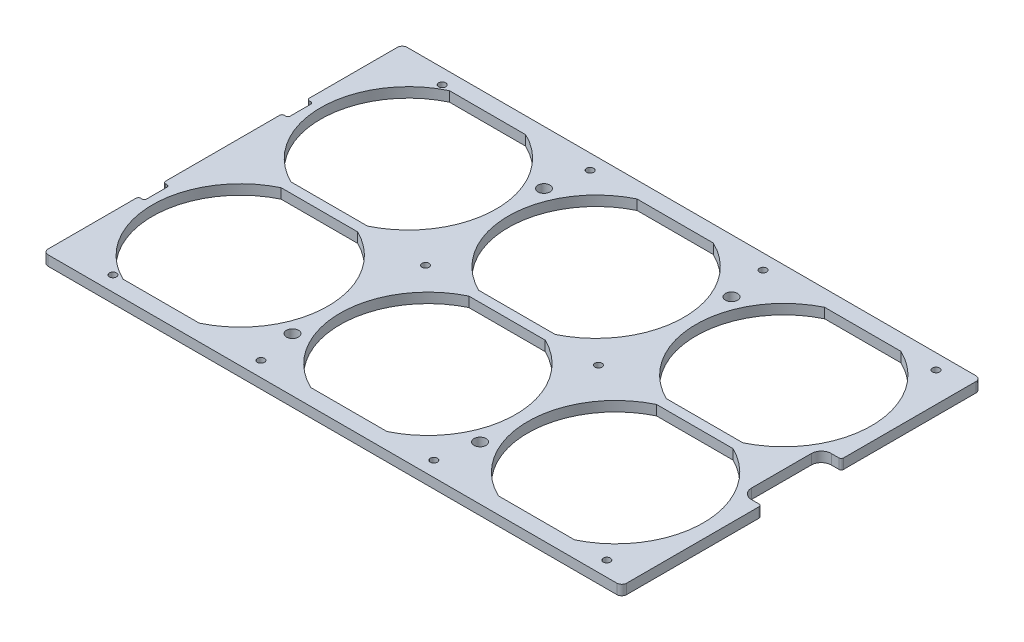
SolidWorks part; units mm, degrees
material "NEOPRENE"
ref_plane "Front" through (0, 0, 0) normal (0, 0, 1) x (1, 0, 0)
ref_plane "Top" through (0, 0, 0) normal (0, 1, 0) x (1, 0, 0)
ref_plane "Right" through (0, 0, 0) normal (1, 0, 0) x (0, 0, -1)
sketch "Sketch1" plane through (0, 0, 0) normal (0, 1, 0) x (1, 0, 0)
  line L0 (-24.3078, -3.1623) -> (24.3078, -3.1623)
  line L1 (-180.975, 114.3) -> (180.975, 114.3)
  line L2 (-184.15, 111.125) -> (-184.15, -111.125)
  line L3 (-180.975, -114.3) -> (180.975, -114.3)
  line L4 (184.15, 111.125) -> (184.15, -111.125)
  line L5 (-184.15, 114.3) -> (184.15, -114.3) construction
  line L6 (-184.15, -114.3) -> (184.15, 114.3) construction
  line L7 (95.1365, -3.1623) -> (143.7521, -3.1623)
  line L8 (95.1365, -3.1623) -> (95.1365, -103.8733) construction
  line L9 (95.1365, -103.8733) -> (143.7521, -103.8733)
  line L10 (143.7521, -3.1623) -> (143.7521, -103.8733) construction
  line L11 (95.1365, -3.1623) -> (143.7521, -103.8733) construction
  line L12 (95.1365, -103.8733) -> (143.7521, -3.1623) construction
  line L13 (-24.3078, -103.8733) -> (24.3078, -103.8733)
  line L14 (-143.7521, -3.1623) -> (-95.1365, -3.1623)
  line L15 (-143.7521, -103.8733) -> (-95.1365, -103.8733)
  line L16 (-24.3078, 103.8733) -> (24.3078, 103.8733)
  line L17 (-24.3078, 3.1623) -> (24.3078, 3.1623)
  line L18 (-143.7521, 103.8733) -> (-95.1365, 103.8733)
  line L19 (-143.7521, 3.1623) -> (-95.1365, 3.1623)
  line L20 (95.1365, 103.8733) -> (143.7521, 103.8733)
  line L21 (95.1365, 3.1623) -> (143.7521, 3.1623)
  line L22 (-95.1365, -103.8733) -> (-24.3078, -103.8733) construction
  line L23 (24.3078, -103.8733) -> (95.1365, -103.8733) construction
  line L24 (119.5086, 53.5178) -> (119.5086, -53.5178) construction
  line L25 (24.3078, 3.1623) -> (24.3078, -3.1623) construction
  line L26 (-175.3235, -53.5178) -> (-184.15, -53.5178) construction
  line L27 (175.3235, -53.5178) -> (184.15, -53.5178) construction
  line L28 (-24.3078, -103.8733) -> (-24.3078, -114.3) construction
  line L29 (-24.3078, 103.8733) -> (-24.3078, 114.3) construction
  arc A0 (95.1365, -3.1623) -> (95.1365, -103.8733) centre (119.5086, -53.5178) ccw
  arc A1 (143.7521, -3.1623) -> (143.7521, -103.8733) centre (119.38, -53.5178) cw
  arc A2 (-184.15, -111.125) -> (-180.975, -114.3) centre (-180.975, -111.125) ccw
  arc A3 (184.15, -111.125) -> (180.975, -114.3) centre (180.975, -111.125) cw
  arc A4 (184.15, 111.125) -> (180.975, 114.3) centre (180.975, 111.125) ccw
  arc A5 (-180.975, 114.3) -> (-184.15, 111.125) centre (-180.975, 111.125) ccw
  circle A6 centre (-149.225, -104.775) radius 2.2479 construction
  circle A8 centre (-55.0333, -104.775) radius 2.2479 construction
  arc A10 (-24.3078, -3.1623) -> (-24.3078, -103.8733) centre (0.0643, -53.5178) ccw
  arc A11 (24.3078, -3.1623) -> (24.3078, -103.8733) centre (-0.0643, -53.5178) cw
  arc A12 (-143.7521, -3.1623) -> (-143.7521, -103.8733) centre (-119.38, -53.5178) ccw
  arc A13 (-95.1365, -3.1623) -> (-95.1365, -103.8733) centre (-119.5086, -53.5178) cw
  arc A14 (-24.3078, 103.8733) -> (-24.3078, 3.1623) centre (0.0643, 53.5178) ccw
  arc A15 (24.3078, 103.8733) -> (24.3078, 3.1623) centre (-0.0643, 53.5178) cw
  arc A16 (-143.7521, 103.8733) -> (-143.7521, 3.1623) centre (-119.38, 53.5178) ccw
  arc A17 (-95.1365, 103.8733) -> (-95.1365, 3.1623) centre (-119.5086, 53.5178) cw
  arc A18 (95.1365, 103.8733) -> (95.1365, 3.1623) centre (119.5086, 53.5178) ccw
  arc A19 (143.7521, 103.8733) -> (143.7521, 3.1623) centre (119.38, 53.5178) cw
  circle A20 centre (55.0333, -104.775) radius 2.2479 construction
  circle A21 centre (165.1, -104.775) radius 2.2479 construction
  circle A22 centre (165.1, 104.775) radius 2.2479 construction
  circle A23 centre (55.0333, 104.775) radius 2.2479 construction
  circle A24 centre (-55.0333, 104.775) radius 2.2479 construction
  circle A25 centre (-149.225, 104.775) radius 2.2479 construction
  circle A26 centre (-149.225, -104.775) radius 2.2479
  circle A27 centre (-55.0333, -104.775) radius 2.2479
  circle A28 centre (55.0333, -104.775) radius 2.2479
  circle A29 centre (165.1, -104.775) radius 2.2479
  circle A30 centre (165.1, 104.775) radius 2.2479
  circle A31 centre (55.0333, 104.775) radius 2.2479
  circle A32 centre (-55.0333, 104.775) radius 2.2479
  circle A33 centre (-149.225, 104.775) radius 2.2479
  circle A34 centre (59.69, 80.01) radius 1.8288 construction
  circle A35 centre (-59.69, 80.01) radius 1.8288 construction
  circle A36 centre (-55.0333, 0) radius 2.2479 construction
  circle A37 centre (55.0333, 0) radius 2.2479 construction
  circle A38 centre (59.69, -80.01) radius 1.8288 construction
  circle A39 centre (-59.69, -80.01) radius 1.8288 construction
  circle A40 centre (59.69, 80.01) radius 1.8288 construction
  circle A41 centre (-59.69, 80.01) radius 1.8288 construction
  circle A42 centre (-55.0333, 0) radius 2.2479
  circle A43 centre (55.0333, 0) radius 2.2479
  circle A44 centre (59.69, -80.01) radius 1.8288 construction
  circle A45 centre (-59.69, -80.01) radius 1.8288 construction
  circle A46 centre (-59.69, 80.01) radius 3.81
  circle A47 centre (-59.69, -80.01) radius 3.81
  circle A48 centre (59.69, -80.01) radius 3.81
  circle A49 centre (59.69, 80.01) radius 3.81
  point P0 (0, 0)
  point P6 (119.4443, -53.5178)
  dimension "D4" = 111.887
  dimension "D8" = 3.175
  dimension "D9" = 7.62
  dimension "D1" = 368.3
  dimension "D2" = 228.6
  dimension "D3" = 100.711
  dimension "D5" = 48.6156
  dimension "D6" = 119.38
  dimension "D7" = 107.0356
  dimension "D11" = 3
  dimension "D12" = 2
extrude "Boss-Extrude1" add sketch "Sketch1" along normal blind 6.35
sketch "Sketch2" plane through (0, 6.35, 0) normal (0, 1, 0) x (1, 0, 0)
  line L0 (0, 0) -> (184.15, 0) construction
  line L1 (184.15, -111.125) -> (184.15, 111.125) construction
  line L2 (184.15, -111.125) -> (184.15, 111.125) construction
  line L3 (184.15, 25.4) -> (177.8, 25.4)
  line L4 (184.15, 25.4) -> (184.15, -25.4)
  line L5 (184.15, -25.4) -> (177.8, -25.4)
  line L6 (171.45, 19.05) -> (171.45, -19.05)
  arc A0 (177.8, -25.4) -> (171.45, -19.05) centre (177.8, -19.05) cw
  arc A1 (177.8, 25.4) -> (171.45, 19.05) centre (177.8, 19.05) ccw
  point P14 (171.45, -25.4)
  point P17 (171.45, 25.4)
  dimension "D3" = 6.35
  dimension "D1" = 12.7
  dimension "D2" = 50.8
extrude "Cut-Extrude1" cut sketch "Sketch2" against normal through all and the other way through all
sketch "Sketch3" plane through (0, 6.35, 0) normal (0, 1, 0) x (1, 0, 0)
  line L0 (-184.15, 111.125) -> (-184.15, -111.125) construction
  line L1 (-184.15, 53.6575) -> (-180.34, 53.6575)
  line L2 (-184.15, 53.6575) -> (-184.15, 37.7825)
  line L3 (-184.15, 37.7825) -> (-180.34, 37.7825)
  line L4 (-180.34, 53.6575) -> (-180.34, 37.7825)
  line L5 (-180.34, 45.72) -> (-184.15, 45.72) construction
  line L6 (0, 0) -> (-184.15, 0) construction
  line L8 (-184.15, -37.7825) -> (-180.34, -37.7825)
  line L9 (-180.34, -53.6575) -> (-180.34, -37.7825)
  line L10 (-184.15, -53.6575) -> (-180.34, -53.6575)
  line L11 (-184.15, -53.6575) -> (-184.15, -37.7825)
  dimension "D1" = 3.81
  dimension "D2" = 15.875
  dimension "D3" = 45.72
extrude "Cut-Extrude2" cut sketch "Sketch3" against normal through all
fillet "Fillet1" radius 1.524 10 edges at (184.15, 3.175, 25.4) (184.15, 3.175, -25.4) (-180.34, 3.175, 37.7825) (-184.15, 3.175, 37.7825) (-184.15, 3.175, 53.6575) (-180.34, 3.175, 53.6575) (-184.15, 3.175, -37.7825) (-180.34, 3.175, -37.7825) (-184.15, 3.175, -53.6575) (-180.34, 3.175, -53.6575)
